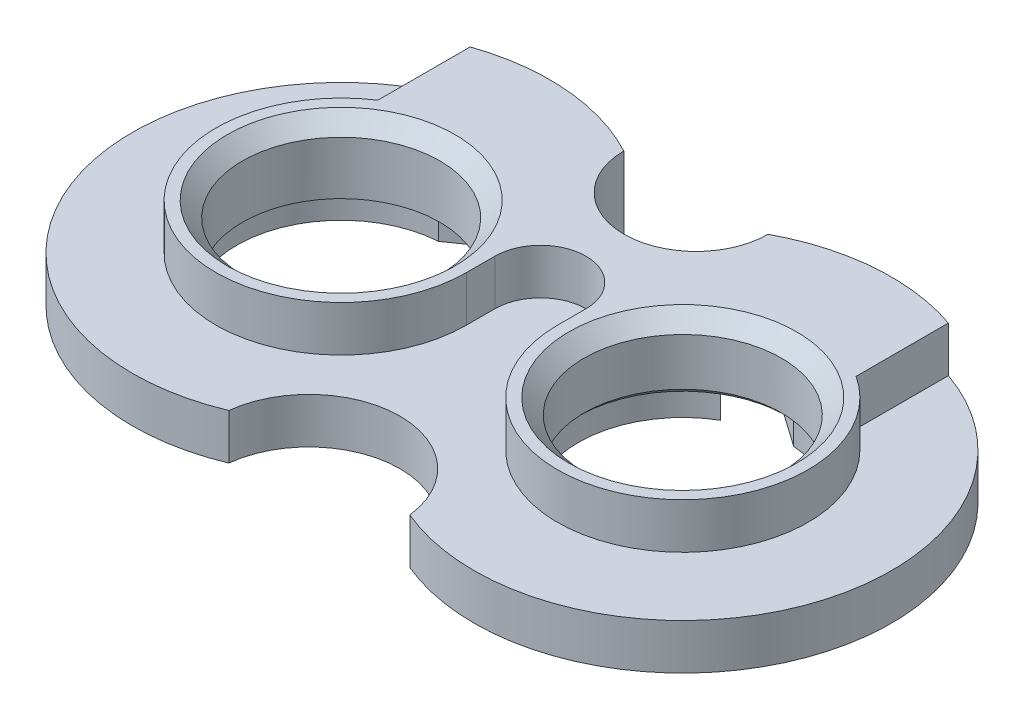
SolidWorks part; units mm, degrees
material "АЛ8Т4 ГОСТ 1583-93"
ref_plane "Спереди" through (0, 0, 0) normal (0, 0, 1) x (1, 0, 0)
ref_plane "Сверху" through (0, 0, 0) normal (0, 1, 0) x (1, 0, 0)
ref_plane "Справа" through (0, 0, 0) normal (1, 0, 0) x (0, 0, -1)
sketch "Эскиз1" plane through (0, 0, 0) normal (0, 1, 0) x (1, 0, 0)
  line L0 (0, 0) -> (0, 15.8114) construction
  arc A0 (0, -15.8114) -> (0, 15.8114) centre (22.5, 0) ccw
  arc A1 (0, 15.8114) -> (0, -15.8114) centre (-22.5, 0) ccw
  point P4 (-50, 0)
  point P5 (50, 0)
  dimension "D2" = 55
  dimension "D3" = 100
extrude "Бобышка-Вытянуть1" add sketch "Эскиз1" along normal blind 12
sketch "Эскиз2" plane through (0, 0, 0) normal (0, 1, 0) x (1, 0, 0)
  circle A0 centre (0, 24.25) radius 9.5
  circle A1 centre (0, -26.75) radius 12
  point P4 (0, 14.75)
  point P5 (0, -14.75)
  dimension "D1" = 19
  dimension "D2" = 24
  dimension "D3" = 29.5
  dimension "D4" = 14.75
extrude "Вырез-Вытянуть1" cut sketch "Эскиз2" along normal through all
sketch "Эскиз3" plane through (0, 12, 0) normal (0, 1, 0) x (1, 0, 0)
  line L0 (-6, 0) -> (-6, 3.75)
  line L1 (31.5, 40) -> (31.5, 13.8293)
  line L2 (6, 0) -> (6, 3.75)
  line L3 (-31.5, 40) -> (-31.5, 13.8293)
  line L4 (-31.5, 40) -> (-71.5, 40)
  line L5 (-71.5, 40) -> (-71.5, -30)
  line L6 (-71.5, -30) -> (71.5, -30)
  line L7 (71.5, -30) -> (71.5, 40)
  line L8 (71.5, 40) -> (31.5, 40)
  arc A0 (-31.5, 13.8293) -> (-6, 0) centre (-22.5, 0) ccw
  arc A1 (6, 0) -> (31.5, 13.8293) centre (22.5, 0) ccw
  arc A2 (-6, 3.75) -> (6, 3.75) centre (0, 3.75) cw
  arc A3 (-9.5, 24.2332) -> (9.5, 24.2332) centre (0, 24.25) ccw construction
  point P11 (0, 9.75)
  point P12 (0, 14.75)
  dimension "D1" = 33
  dimension "D2" = 33
  dimension "D3" = 5
  dimension "D4" = 31.5
  dimension "D5" = 31.5
  dimension "D6" = 70
  dimension "D7" = 40
  dimension "D8" = 40
  dimension "D9" = 30
extrude "Вырез-Вытянуть2" cut sketch "Эскиз3" against normal blind 6
sketch "Эскиз4" plane through (0, 0, 0) normal (0, 1, 0) x (1, 0, 0)
  circle A0 centre (-22.5, 0) radius 13
  circle A1 centre (22.5, 0) radius 13
  dimension "D1" = 26
  dimension "D2" = 26
extrude "Вырез-Вытянуть3" cut sketch "Эскиз4" along normal through all
chamfer "Фаска1" distance 2 angle 45 2 edges at (22.5, 12, 13) (-22.5, 12, 13)
sketch "Эскиз5" plane through (0, 0, 0) normal (0, -1, 0) x (1, 0, 0)
  line L0 (-4.5585, -19.5851) -> (-25.0373, -5.2457)
  line L1 (-25.0373, -5.2457) -> (-28.4788, -10.1606)
  line L2 (-28.4788, -10.1606) -> (-8, -24.5)
  line L3 (-8, -24.5) -> (-4.5585, -19.5851)
  line L4 (4.5585, -19.5851) -> (25.0373, -5.2457)
  line L5 (25.0373, -5.2457) -> (28.4788, -10.1606)
  line L6 (28.4788, -10.1606) -> (8, -24.5)
  line L7 (8, -24.5) -> (4.5585, -19.5851)
  line L8 (0, 0) -> (0, -30) construction
  line L9 (0, -30) -> (-30.6519, -30) construction
  dimension "D1" = 6
  dimension "D2" = 6
  dimension "D3" = 35
  dimension "D4" = 35
  dimension "D5" = 25
  dimension "D6" = 25
  dimension "D7" = 8
  dimension "D8" = 11
  dimension "D9" = 30
extrude "Вырез-Вытянуть4" cut sketch "Эскиз5" against normal blind 3
sketch "Эскиз7" plane through (0, 0, 0) normal (0, -1, 0) x (1, 0, 0)
  circle A0 centre (-22.5, 0) radius 13.75
  circle A1 centre (22.5, 0) radius 13.75
  dimension "D1" = 27.5
  dimension "D2" = 27.5
extrude "Вырез-Вытянуть5" cut sketch "Эскиз7" against normal blind 3
chamfer "Фаска2" distance 0.75 angle 45 1 edges at (22.5, 3, 13)
